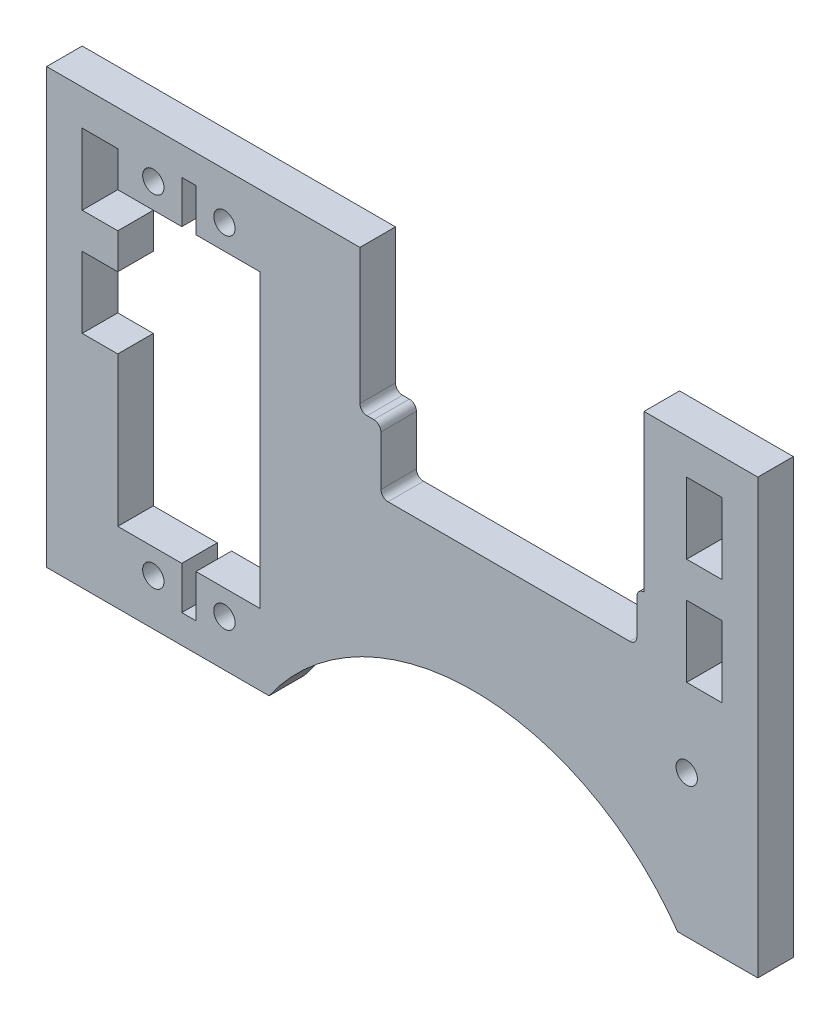
SolidWorks part; units mm, degrees
ref_plane "Plan de face" through (0, 0, 0) normal (0, 0, 1) x (1, 0, 0)
ref_plane "Plan de dessus" through (0, 0, 0) normal (0, 1, 0) x (1, 0, 0)
ref_plane "Plan de droite" through (0, 0, 0) normal (1, 0, 0) x (0, 0, -1)
sketch "Esquisse1" plane through (0, 0, 0) normal (0, 0, 1) x (1, 0, 0)
  line L0 (20, 71) -> (20, 0) construction
  line L1 (0, 0) -> (31.2772, 0)
  line L2 (0, 0) -> (0, 61)
  line L3 (0, 61) -> (44.05, 61)
  line L4 (100, 0) -> (100, 61)
  line L5 (10, 30.5) -> (30, 30.5) construction
  line L6 (10, 51) -> (19, 51)
  line L7 (10, 46) -> (10, 41)
  line L8 (10, 10) -> (19, 10)
  line L9 (30, 51) -> (30, 10)
  line L10 (20, 20) -> (90, 20) construction
  line L11 (88.7228, 0) -> (100, 0)
  line L12 (21, 4) -> (21, 10)
  line L13 (19, 57) -> (21, 57)
  line L14 (19, 57) -> (19, 51)
  line L15 (21, 10) -> (30, 10)
  line L16 (21, 57) -> (21, 51)
  line L17 (19, 4) -> (21, 4)
  line L18 (19, 4) -> (19, 10)
  line L19 (21, 51) -> (30, 51)
  line L20 (10, 31) -> (10, 10)
  line L21 (90, 56) -> (95, 56)
  line L22 (90, 56) -> (90, 46)
  line L23 (90, 46) -> (95, 46)
  line L24 (95, 56) -> (95, 46)
  line L25 (90, 41) -> (95, 41)
  line L26 (90, 41) -> (90, 31)
  line L27 (90, 31) -> (95, 31)
  line L28 (95, 41) -> (95, 31)
  line L29 (5, 56) -> (10, 56)
  line L30 (5, 56) -> (5, 46)
  line L31 (5, 46) -> (10, 46)
  line L32 (10, 56) -> (10, 51)
  line L33 (5, 41) -> (10, 41)
  line L34 (5, 41) -> (5, 31)
  line L35 (5, 31) -> (10, 31)
  line L36 (84, 61) -> (100, 61)
  line L37 (47, 41) -> (44.05, 41)
  line L38 (84, 61) -> (84, 39)
  line L39 (84, 39) -> (83, 39)
  line L40 (44.05, 61) -> (44.05, 41)
  line L42 (83, 39) -> (83, 32)
  line L43 (83, 32) -> (47, 32)
  line L44 (47, 41) -> (47, 32)
  circle A0 centre (15, 6.5) radius 1.5
  circle A1 centre (25, 6.5) radius 1.5
  circle A2 centre (25, 54.5) radius 1.5
  circle A3 centre (15, 54.5) radius 1.5
  circle A4 centre (20, 20) radius 1.5 construction
  circle A5 centre (20, 20) radius 1.5 construction
  circle A6 centre (90, 20) radius 1.5
  circle A7 centre (60, -20) radius 35 construction
  arc A8 (31.2772, 0) -> (88.7228, 0) centre (60, -20) cw
  dimension "D6" = 3.5
  dimension "D8" = 3
  dimension "D9" = 3
  dimension "D10" = 70
  dimension "D13" = 70
  dimension "D16" = 2
  dimension "D1" = 10
  dimension "D2" = 41
  dimension "D3" = 20
  dimension "D4" = 10
  dimension "D5" = 100
  dimension "D7" = 5
  dimension "D11" = 10
  dimension "D12" = 10
  dimension "D14" = 40
  dimension "D15" = 40
  dimension "D17" = 6
  dimension "D18" = 5
  dimension "D19" = 5
  dimension "D20" = 10
  dimension "D21" = 5
  dimension "D22" = 5
  dimension "D23" = 5
  dimension "D24" = 10
  dimension "D25" = 6
  dimension "D26" = 20
  dimension "D27" = 40
  dimension "D28" = 1
  dimension "D29" = 36
  dimension "D30" = 9
  dimension "D31" = 22
  dimension "D32" = 7
extrude "Boss.-Extru.1" add sketch "Esquisse1" along normal blind 5
fillet "Congé1" radius 1 5 edges at (83, 39, 2.5) (83, 32, 2.5) (47, 32, 2.5) (47, 41, 2.5) (44.05, 41, 2.5)
